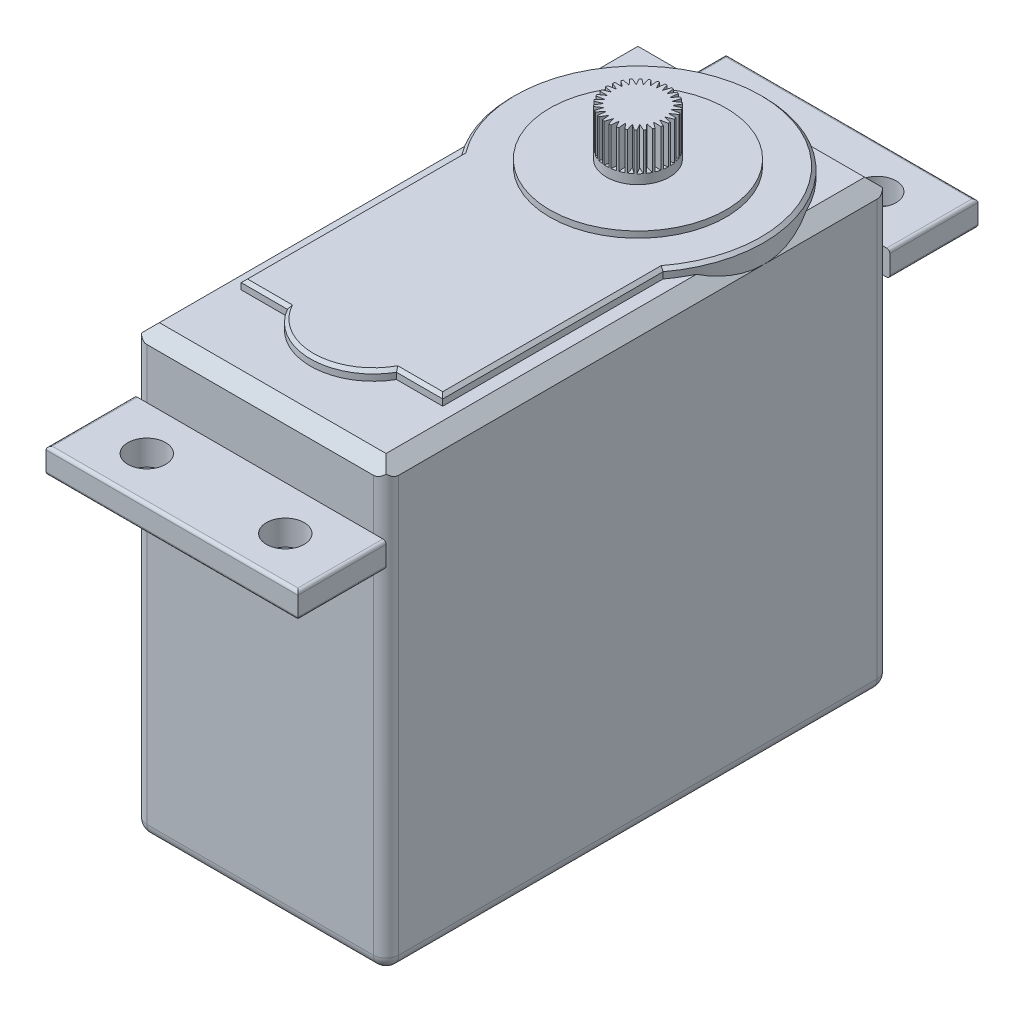
SolidWorks part; units mm, degrees
ref_plane "Front Plane" through (0, 0, 0) normal (0, 0, 1) x (1, 0, 0)
ref_plane "Top Plane" through (0, 0, 0) normal (0, 1, 0) x (1, 0, 0)
ref_plane "Right Plane" through (0, 0, 0) normal (1, 0, 0) x (0, 0, -1)
sketch "Sketch1" plane through (0, 0, 0) normal (0, 1, 0) x (1, 0, 0)
  line L0 (-10, 10) -> (10, 10)
  line L1 (-10, 10) -> (-10, -30)
  line L2 (10, 10) -> (10, -30)
  line L3 (-10, -30) -> (10, -30)
  line L4 (-10, 10) -> (10, -30) construction
  line L5 (10, 10) -> (-10, -30) construction
  line L6 (-17.0154, -10) -> (17.0154, -10) construction
  line L7 (-10, 10) -> (10, 10)
  line L8 (-10, 10) -> (-10, 17)
  line L9 (-10, 17) -> (10, 17)
  line L10 (10, 10) -> (10, 17)
  line L11 (10, -30) -> (-10, -30)
  line L12 (10, -30) -> (10, -37)
  line L13 (10, -37) -> (-10, -37)
  line L14 (-10, -30) -> (-10, -37)
  circle A0 centre (-5.5, 13.5) radius 1.5
  circle A1 centre (5.5, 13.5) radius 1.5
  circle A2 centre (5.5, -33.5) radius 1.5
  circle A3 centre (-5.5, -33.5) radius 1.5
  point P0 (0, 10)
  point P1 (0, -10)
  point P16 (-10, 13.5)
  point P18 (0, 17)
  point P23 (0, -10)
  dimension "D5" = 3
  dimension "D1" = 10
  dimension "D2" = 20
  dimension "D3" = 40
  dimension "D4" = 7
  dimension "D6" = 11
  dimension "D7" = 5.5
extrude "Boss-Extrude1" add sketch "Sketch1" against normal blind 30 and the other way blind 5 contours L1 L3 L2 L0 region at (0, 0, 10)
extrude "Boss-Extrude2" add sketch "Sketch1<6>" against normal blind 2 separate body contours L3 L14 L13 L12 | L0 L10 L9 L8 region at (0, 0, -13.5) region at (0, 0, 33.5)
sketch "Sketch1<6>" plane through (0, 0, 0) normal (0, 1, 0) x (1, 0, 0) same geometry as "Sketch1"
sketch "Sketch2" plane through (0, 5, 0) normal (0, 1, 0) x (1, 0, 0)
  line L0 (-8, -3.5) -> (8, -3.5)
  line L1 (-8, -3.5) -> (-8, -23.5)
  line L2 (8, -3.5) -> (8, -23.5)
  line L3 (-8, -23.5) -> (8, -23.5)
  line L4 (-10, -30) -> (10, -30) construction
  line L5 (-0.1764, 2.4938) -> (0, 1.9307)
  line L6 (-10, 10) -> (-10, -30) construction
  line L7 (0, 1.9307) -> (0.1897, 2.4928)
  line L8 (0.4014, 1.8885) -> (0.7038, 2.3989)
  line L9 (0.3459, 2.4759) -> (0.4014, 1.8885)
  line L10 (0.7853, 1.7638) -> (1.1872, 2.2001)
  line L11 (0.8532, 2.3499) -> (0.7853, 1.7638)
  line L12 (1.1348, 1.562) -> (1.6187, 1.9052)
  line L13 (1.3231, 2.1212) -> (1.1348, 1.562)
  line L14 (1.4348, 1.2919) -> (1.9794, 1.5271)
  line L15 (1.7352, 1.7997) -> (1.4348, 1.2919)
  line L16 (1.672, 0.9654) -> (2.2537, 1.0822)
  line L17 (2.0715, 1.3996) -> (1.672, 0.9654)
  line L18 (1.8362, 0.5966) -> (2.4294, 0.5899)
  line L19 (2.3172, 0.9384) -> (1.8362, 0.5966)
  line L20 (1.9201, 0.2018) -> (2.499, 0.072)
  line L21 (2.4617, 0.4361) -> (1.9201, 0.2018)
  line L22 (1.9201, -0.2018) -> (2.4593, -0.4492)
  line L23 (2.4985, -0.0852) -> (1.9201, -0.2018)
  line L24 (1.8362, -0.5966) -> (2.3122, -0.9507)
  line L25 (2.4262, -0.6029) -> (1.8362, -0.5966)
  line L26 (1.672, -0.9654) -> (2.064, -1.4106)
  line L27 (2.2479, -1.0941) -> (1.672, -0.9654)
  line L28 (1.4348, -1.2919) -> (1.7256, -1.8089)
  line L29 (1.9713, -1.5376) -> (1.4348, -1.2919)
  line L30 (1.1348, -1.562) -> (1.3118, -2.1282)
  line L31 (1.6085, -1.9138) -> (1.1348, -1.562)
  line L32 (0.7853, -1.7638) -> (0.8407, -2.3544)
  line L33 (1.1755, -2.2064) -> (0.7853, -1.7638)
  line L34 (0.4014, -1.8885) -> (0.3328, -2.4778)
  line L35 (0.691, -2.4026) -> (0.4014, -1.8885)
  line L36 (0, -1.9307) -> (-0.1897, -2.4928)
  line L37 (0.1764, -2.4938) -> (0, -1.9307)
  line L38 (-0.4014, -1.8885) -> (-0.7038, -2.3989)
  line L39 (-0.3459, -2.4759) -> (-0.4014, -1.8885)
  line L40 (-0.7853, -1.7638) -> (-1.1872, -2.2001)
  line L41 (-0.8532, -2.3499) -> (-0.7853, -1.7638)
  line L42 (-1.1348, -1.562) -> (-1.6187, -1.9052)
  line L43 (-1.3231, -2.1212) -> (-1.1348, -1.562)
  line L44 (-1.4348, -1.2919) -> (-1.9794, -1.5271)
  line L45 (-1.7352, -1.7997) -> (-1.4348, -1.2919)
  line L46 (-1.672, -0.9654) -> (-2.2537, -1.0822)
  line L47 (-2.0715, -1.3996) -> (-1.672, -0.9654)
  line L48 (-1.8362, -0.5966) -> (-2.4294, -0.5899)
  line L49 (-2.3172, -0.9384) -> (-1.8362, -0.5966)
  line L50 (-1.9201, -0.2018) -> (-2.499, -0.072)
  line L51 (-2.4617, -0.4361) -> (-1.9201, -0.2018)
  line L52 (-1.9201, 0.2018) -> (-2.4593, 0.4492)
  line L53 (-2.4985, 0.0852) -> (-1.9201, 0.2018)
  line L54 (-1.8362, 0.5966) -> (-2.3122, 0.9507)
  line L55 (-2.4262, 0.6029) -> (-1.8362, 0.5966)
  line L56 (-1.672, 0.9654) -> (-2.064, 1.4106)
  line L57 (-2.2479, 1.0941) -> (-1.672, 0.9654)
  line L58 (-1.4348, 1.2919) -> (-1.7256, 1.8089)
  line L59 (-1.9713, 1.5376) -> (-1.4348, 1.2919)
  line L60 (-1.1348, 1.562) -> (-1.3118, 2.1282)
  line L61 (-1.6085, 1.9138) -> (-1.1348, 1.562)
  line L62 (-0.7853, 1.7638) -> (-0.8407, 2.3544)
  line L63 (-1.1755, 2.2064) -> (-0.7853, 1.7638)
  line L64 (-0.4014, 1.8885) -> (-0.3328, 2.4778)
  line L65 (-0.691, 2.4026) -> (-0.4014, 1.8885)
  arc A0 (8, -6) -> (-8, -6) centre (0, 0) ccw
  circle A1 centre (0, 0) radius 7
  circle A2 centre (0, 0) radius 2.5
  circle A3 centre (0, -21) radius 5
  circle A4 centre (0, 0) radius 2.5
  point P5 (0, -3.5)
  point P13 (0, -23.5)
  point P113 (0, 0)
  dimension "D1" = 5
  dimension "D2" = 14
  dimension "D6" = 10
  dimension "D7" = 10
  dimension "D3" = 2
  dimension "D4" = 3.5
  dimension "D5" = 6.5
  dimension "D8" = 2.5
  dimension "D9" = 30
extrude "Boss-Extrude3" add sketch "Sketch2" along normal blind 0.75 contours L3 A3 | L3 A3 | A3 L3 L2 L0 A1 L1 | A1 L0 L2 A0 L1 region at (-8.2561, 5, 4.75) region at (0, 5, 12.7855) region at (0, 5, 20.1434) region at (0, 5, 24.5251)
extrude "Boss-Extrude4" add sketch "Sketch2<3>" along normal blind 1.25 contours L0 A1 | L0 A1 A2 region at (-1.7664, 5, -6.5924) region at (0, 5, 4.9351)
sketch "Sketch2<3>" plane through (0, 5, 0) normal (0, 1, 0) x (1, 0, 0) same geometry as "Sketch2"
extrude "Boss-Extrude5" add sketch "Sketch2<4>" along normal blind 5 contours L37 A2 L34 L35 L32 L33 L30 L31 L28 L29 L26 L27 L24 L25 L22 L23 L20 L21 L18 L19 L16 L17 L14 L15 L12 L13 L10 L11 L8 L9 L7 L5 L64 L65 L62 region at (0, 5, 0)
sketch "Sketch2<4>" plane through (0, 5, 0) normal (0, 1, 0) x (1, 0, 0) same geometry as "Sketch2"
extrude "Boss-Extrude6" add sketch "Sketch2<5>" along normal blind 2 contours A2
sketch "Sketch2<5>" plane through (0, 5, 0) normal (0, 1, 0) x (1, 0, 0) same geometry as "Sketch2"
chamfer "Chamfer1" distance 0.25 angle 45 6 edges at (0, 5.75, 26) (6.1651, 5.75, 23.5) (8, 5.75, 14.75) (0, 5.75, -10) (-8, 5.75, 14.75) (-6.1651, 5.75, 23.5)
chamfer "Chamfer2" distance 1 angle 45 7 edges at (-5, 5, -10) (5, 5, -10) (-10, 5, 15) (-10, 5, -5) (10, 5, -5) (10, 5, 15) (0, 5, 30)
fillet "Fillet1" radius 1 8 edges at (0, -30, -10) (-10, -30, 10) (0, -30, 30) (10, -30, 10) (-10, -13, -10) (-10, -13, 30) (10, -13, -10) (10, -13, 30)
fillet "Fillet2" radius 0.25 6 edges at (-10, 0, 33.5) (-10, -2, 33.5) (0, -2, 37) (10, -2, 33.5) (10, 0, 33.5) (0, 0, 37)
fillet "Fillet3" radius 0.25 6 edges at (-10, -2, -13.5) (-10, 0, -13.5) (10, -2, -13.5) (10, 0, -13.5) (0, -2, -17) (0, 0, -17)
